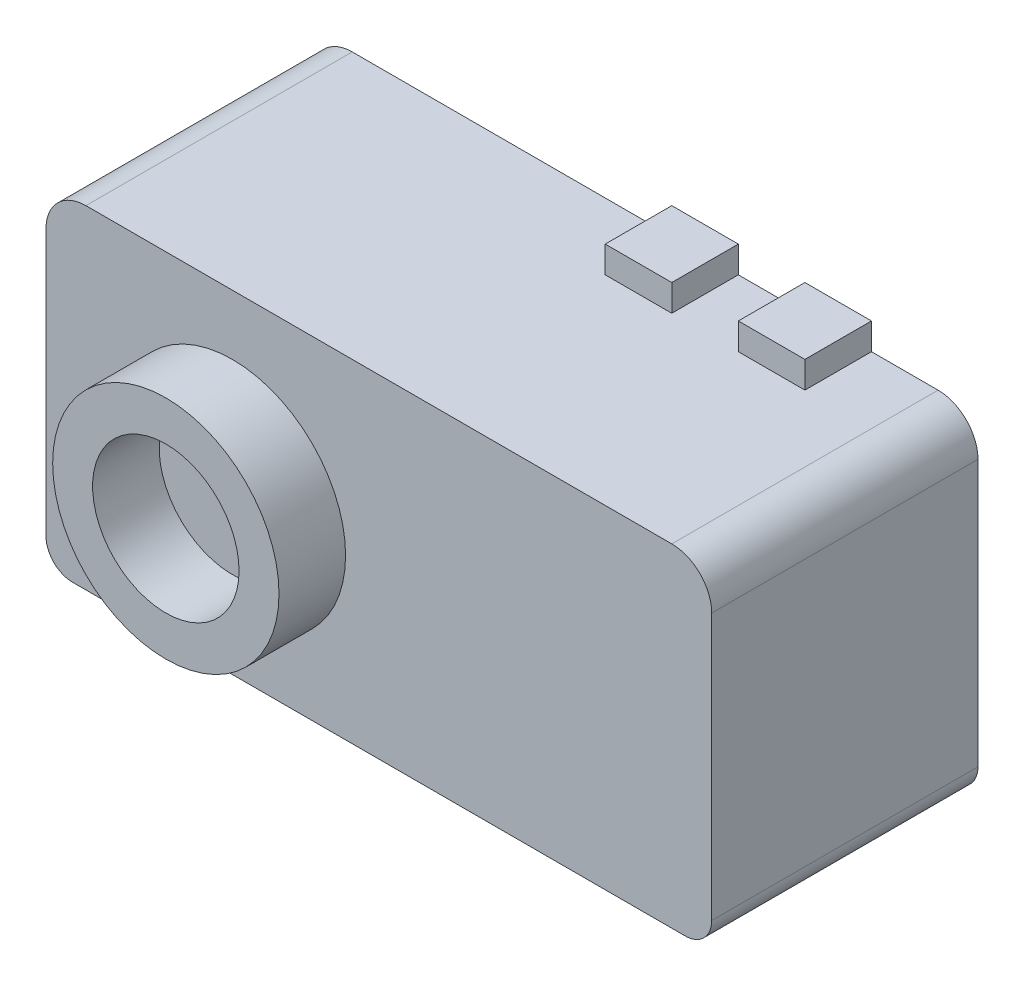
SolidWorks part; units mm, degrees
material "PET"
ref_plane "Front Plane" through (0, 0, 0) normal (0, 0, 1) x (1, 0, 0)
ref_plane "Top Plane" through (0, 0, 0) normal (0, 1, 0) x (1, 0, 0)
ref_plane "Right Plane" through (0, 0, 0) normal (1, 0, 0) x (0, 0, -1)
sketch "Sketch1" plane through (0, 0, 0) normal (0, 0, 1) x (1, 0, 0)
  line L0 (-25, 10) -> (-25, -10)
  line L1 (-23, -12) -> (23, -12)
  line L2 (25, -10) -> (25, 10)
  line L3 (22, 13) -> (17, 13)
  line L4 (17, 13) -> (17, 15)
  line L5 (17, 15) -> (12, 15)
  line L6 (12, 15) -> (12, 13)
  line L7 (12, 13) -> (7, 13)
  line L8 (7, 13) -> (7, 15)
  line L9 (7, 15) -> (2, 15)
  line L10 (2, 15) -> (2, 13)
  line L11 (2, 13) -> (-22, 13)
  line L12 (-25, 0) -> (25, 0) construction
  arc A0 (25, 10) -> (22, 13) centre (22, 10) ccw
  arc A1 (-22, 13) -> (-25, 10) centre (-22, 10) ccw
  arc A2 (25, -10) -> (23, -12) centre (23, -10) cw
  arc A3 (-23, -12) -> (-25, -10) centre (-23, -10) cw
  point P2 (0, 0)
  point P18 (25, 13)
  point P21 (-25, 13)
  point P24 (25, -12)
  point P27 (-25, -12)
  dimension "D7" = 3
  dimension "D8" = 2
  dimension "D1" = 50
  dimension "D2" = 25
  dimension "D3" = 8
  dimension "D4" = 5
  dimension "D5" = 5
  dimension "D6" = 2
extrude "Boss-Extrude1" add sketch "Sketch1" along normal blind 20
sketch "Sketch2" plane through (0, 0, 20) normal (0, 0, 1) x (1, 0, 0)
  line L1 (2, 15) -> (7, 15)
  line L2 (2, 15) -> (2, 13)
  line L3 (2, 13) -> (7, 13)
  line L4 (7, 15) -> (7, 13)
  line L5 (12, 15) -> (17, 15)
  line L6 (12, 15) -> (12, 13)
  line L7 (12, 13) -> (17, 13)
  line L8 (17, 15) -> (17, 13)
extrude "Cut-Extrude1" cut sketch "Sketch2" against normal blind 15
sketch "Sketch3" plane through (0, 0, 20) normal (0, 0, 1) x (1, 0, 0)
  line L0 (-25, 10) -> (-25, -10) construction
  circle A0 centre (-11, 0) radius 5.5
  circle A1 centre (-11, 0) radius 8.5
  dimension "D1" = 17
  dimension "D2" = 11
  dimension "D3" = 14
extrude "Boss-Extrude2" add sketch "Sketch3" along normal blind 5
sketch "Sketch4" plane through (0, -12, 0) normal (0, -1, 0) x (1, 0, 0)
  line L0 (-5.5, 0) -> (-5.5, 9)
  line L1 (-23, 0) -> (23, 0) construction
  line L2 (-5.5, 9) -> (5.5, 9)
  line L3 (5.5, 9) -> (5.5, 0)
  line L4 (5.5, 0) -> (-5.5, 0)
  point P4 (0, 0)
  point P8 (0, 0)
  dimension "D1" = 9
  dimension "11" = 11
extrude "Boss-Extrude3" add sketch "Sketch4" along normal blind 10
sketch "Sketch5" plane through (5.5, 0, 0) normal (1, 0, 0) x (0, 0, -1)
  line L0 (-9, -22) -> (-9, -12) construction
  line L1 (-9, -22) -> (-6, -22)
  line L2 (-9, -22) -> (-9, -19)
  line L3 (-9, -19) -> (-6, -19)
  line L4 (-6, -22) -> (-6, -19)
  line L5 (0, -22) -> (-3, -22)
  line L6 (0, -22) -> (0, -19)
  line L7 (0, -19) -> (-3, -19)
  line L8 (-3, -22) -> (-3, -19)
  line L9 (-9, -14) -> (-6, -14)
  line L10 (-9, -14) -> (-9, -17)
  line L11 (-9, -17) -> (-6, -17)
  line L12 (-6, -14) -> (-6, -17)
  line L13 (0, -22) -> (0, -12) construction
  line L14 (-3, -14) -> (0, -14)
  line L15 (-3, -14) -> (-3, -17)
  line L16 (-3, -17) -> (0, -17)
  line L17 (0, -14) -> (0, -17)
  dimension "D1" = 3
  dimension "D2" = 3
  dimension "D3" = 3
  dimension "D4" = 3
extrude "Cut-Extrude2" cut sketch "Sketch5" against normal blind 3
extrude "Cut-Extrude3" cut sketch "Sketch5<2>" against normal blind 3 from offset 8 offset against normal yes
sketch "Sketch5<2>" plane through (5.5, 0, 0) normal (1, 0, 0) x (0, 0, -1) same geometry as "Sketch5"
